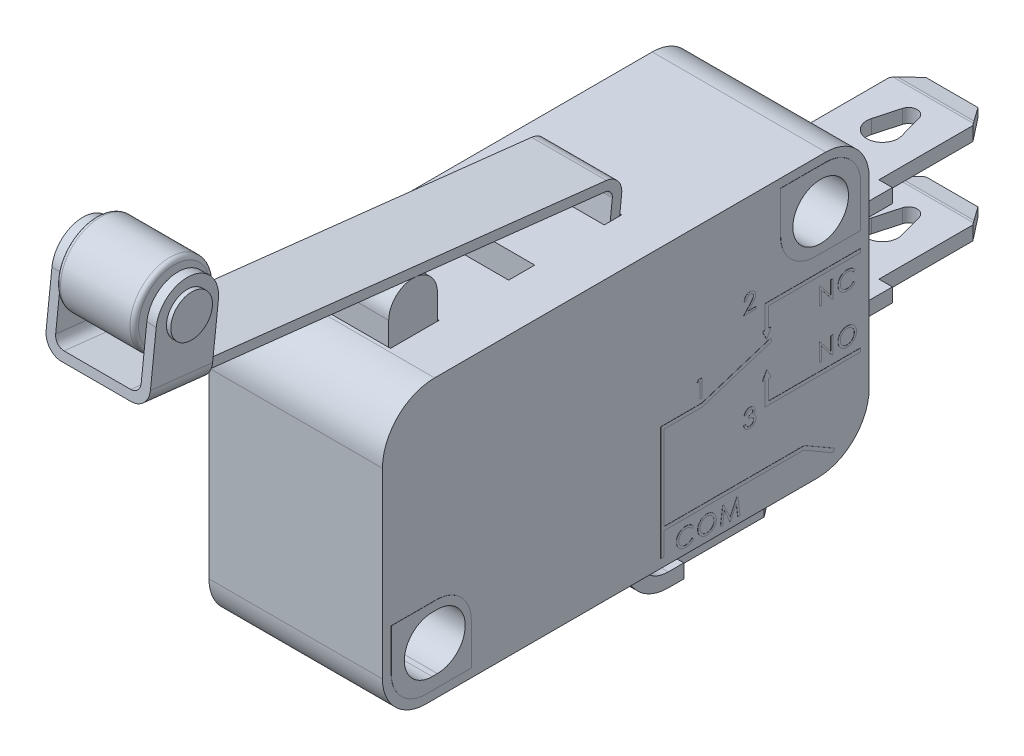
SolidWorks part; units mm, degrees
other "Switch Body"
other "Connections"
other "Lever with Wheel"
material "ABS"
ref_plane "Front Plane" through (0, 0, 0) normal (0, 0, 1) x (1, 0, 0)
ref_plane "Top Plane" through (0, 0, 0) normal (0, 1, 0) x (1, 0, 0)
ref_plane "Right Plane" through (0, 0, 0) normal (1, 0, 0) x (0, 0, -1)
sketch "Sketch1" plane through (0, 0, 0) normal (1, 0, 0) x (0, 0, -1)
  line L0 (-14, 0) -> (0, 0) construction
  line L1 (-11, 8) -> (11.5, 8)
  line L2 (-14, 5) -> (-14, -5.5)
  line L3 (-11.5, -8) -> (11, -8)
  line L4 (14, 5.5) -> (14, -5)
  line L5 (0, 0) -> (14, 0) construction
  line L6 (0, 0) -> (0, -8) construction
  line L7 (0, 0) -> (0, 8) construction
  arc A0 (-11, 8) -> (-14, 5) centre (-11, 5) ccw
  arc A1 (11, -8) -> (14, -5) centre (11, -5) ccw
  arc A2 (-14, -5.5) -> (-11.5, -8) centre (-11.5, -5.5) ccw
  arc A3 (11.5, 8) -> (14, 5.5) centre (11.5, 5.5) cw
  dimension "D3" = 3
  dimension "D4" = 2.5
  dimension "D1" = 28
  dimension "D2" = 16
extrude "Body Extrude" add sketch "Sketch1" along normal mid plane 9.98
sketch "Sketch4" plane through (4.99, 0, 0) normal (1, 0, 0) x (0, 0, -1)
  line L0 (-11.15, -5.2) -> (-10.85, -5.2) construction
  line L1 (-11.15, -3.6) -> (-10.85, -3.6)
  line L2 (-11.15, -6.8) -> (-10.85, -6.8)
  line L3 (-11.15, -5.2) -> (-12.75, -5.2) construction
  line L4 (-10.85, -5.2) -> (-9.25, -5.2) construction
  line L5 (11.2, 5.2) -> (11.2, 6.8) construction
  line L6 (11.2, 6.8) -> (11.2, 8) construction
  line L7 (11.5, 8) -> (-11, 8) construction
  line L8 (11.2, 5.2) -> (12.8, 5.2) construction
  line L9 (12.8, 5.2) -> (14, 5.2) construction
  line L10 (14, -5) -> (14, 5.5) construction
  line L11 (11.2, 5.2) -> (11.2, 3.6) construction
  line L13 (-11.5, -8) -> (11, -8) construction
  line L15 (-14, 5) -> (-14, -5.5) construction
  circle A0 centre (11.2, 5.2) radius 1.6
  arc A1 (-11.15, -3.6) -> (-11.15, -6.8) centre (-11.15, -5.2) ccw
  arc A2 (-10.85, -6.8) -> (-10.85, -3.6) centre (-10.85, -5.2) ccw
  point P4 (-11, -5.2)
  dimension "D1" = 3.2
  dimension "D2" = 3.2
  dimension "D3" = 3.5
  dimension "D4" = 1.2
  dimension "D5" = 1.2
  dimension "D6" = 2.8
  dimension "D7" = 2.8
  dimension "D8" = 11.6
  dimension "D9" = 1.2
  dimension "D10" = 3
  dimension "D11" = 2.8
  dimension "D12" = 11.6
extrude "Mount Holes Cut" cut sketch "Sketch4" against normal up to surface (9.98 mm away) up to face at (-4.99, 0, 0)
sketch "Sketch3" plane through (0, 0, 0) normal (1, 0, 0) x (0, 0, -1)
  line L0 (23.75, 2.5) -> (1.75, 2.5)
  line L1 (1.75, 2.5) -> (1.75, -11)
  line L2 (1.75, -11) -> (11.75, -11)
  line L3 (11.75, -11) -> (11.75, -10.2)
  line L4 (11.75, -10.2) -> (2.55, -10.2)
  line L5 (2.55, -10.2) -> (2.55, -3.25)
  line L6 (2.55, -3.25) -> (23.75, -3.25)
  line L7 (23.75, -3.25) -> (23.75, -2.45)
  line L8 (23.75, -2.45) -> (2.55, -2.45)
  line L9 (2.55, -2.45) -> (2.55, 1.7)
  line L10 (2.55, 1.7) -> (23.75, 1.7)
  line L11 (23.75, 1.7) -> (23.75, 2.5)
  line L12 (23.75, -2.45) -> (23.75, 1.7) construction
  line L13 (2.55, -2.45) -> (2.55, -3.25) construction
  line L14 (11.75, -11) -> (23.75, -11) construction
  line L15 (23.75, -11) -> (23.75, -3.25) construction
  line L16 (11.75, -10.2) -> (23.75, -10.2) construction
  line L17 (14, -5) -> (14, 5.5) construction
  line L18 (11.5, 8) -> (-11, 8) construction
  dimension "D1" = 0.8
  dimension "D2" = 0.8
  dimension "D3" = 10
  dimension "D4" = 12
  dimension "D5" = 5.75
  dimension "D6" = 9.75
  dimension "D7" = 19
  dimension "D8" = 5.5
extrude "Connection Extrude" add sketch "Sketch3" along normal mid plane 6.35 separate body
sketch "Sketch6" plane through (0, 0, -14) normal (0, 0, -1) x (-1, 0, 0)
  line L4 (3.175, 1.7) -> (3.175, 2.5)
  line L5 (3.175, 2.5) -> (-3.175, 2.5)
  line L6 (-3.175, 2.5) -> (-3.175, 1.7)
  line L7 (-3.175, 1.7) -> (3.175, 1.7)
  line L8 (3.175, 1.7) -> (3.175, 2.5)
  line L9 (3.175, 2.5) -> (-3.175, 2.5)
  line L10 (-3.175, 2.5) -> (-3.175, 1.7)
  line L11 (-3.175, 1.7) -> (3.175, 1.7)
  line L12 (3.175, -3.25) -> (3.175, -2.45)
  line L13 (3.175, -2.45) -> (-3.175, -2.45)
  line L14 (-3.175, -2.45) -> (-3.175, -3.25)
  line L15 (-3.175, -3.25) -> (3.175, -3.25)
  line L16 (3.175, -3.25) -> (3.175, -2.45)
  line L17 (3.175, -2.45) -> (-3.175, -2.45)
  line L18 (-3.175, -2.45) -> (-3.175, -3.25)
  line L19 (-3.175, -3.25) -> (3.175, -3.25)
  dimension "D1" = 0
  dimension "D2" = 0
extrude "Connection Cut-1" cut sketch "Sketch6" against normal blind 0.5
sketch "Sketch7" plane through (0, -8, 0) normal (0, -1, 0) x (1, 0, 0)
  line L0 (3.175, -1.75) -> (-3.175, -1.75) construction
  line L1 (-3.175, -1.75) -> (3.175, -1.75)
  line L2 (-3.175, -1.75) -> (-3.175, -2.55)
  line L3 (-3.175, -2.55) -> (3.175, -2.55)
  line L4 (3.175, -1.75) -> (3.175, -2.55)
  line L5 (3.175, -1.75) -> (3.175, -11.75) construction
  line L6 (-3.175, -1.75) -> (-3.175, -11.75) construction
  dimension "D1" = 0.8
extrude "Connection Cut-2" cut sketch "Sketch7" against normal blind 0.5
fillet "Connection Fillet-1" radius 2.5 1 edges at (0, -11, -1.75)
fillet "Connection Fillet-2" radius 1.7 1 edges at (0, -10.2, -2.55)
sketch "Sketch5" plane through (3.175, 0, 0) normal (1, 0, 0) x (0, 0, -1)
  line L0 (23.75, 2.1) -> (22.75, 2.1) construction
  line L1 (23.75, 1.7) -> (23.75, 2.5) construction
  line L2 (23.75, -2.85) -> (22.75, -2.85) construction
  line L3 (23.75, -3.25) -> (23.75, -2.45) construction
  line L4 (11.75, -10.6) -> (10.75, -10.6) construction
  line L5 (11.75, -11) -> (11.75, -10.2) construction
  line L6 (10.75, -11) -> (10.75, -10.2) construction
  line L7 (11.75, -10.2) -> (4.25, -10.2) construction
  line L8 (22.75, -2.45) -> (22.75, -3.25) construction
  line L9 (23.75, -2.45) -> (2.55, -2.45) construction
  line L10 (22.75, 2.5) -> (22.75, 1.7) construction
  line L11 (23.75, 2.5) -> (1.75, 2.5) construction
  line L12 (11.75, -10.35) -> (11.75, -10.85) construction
  line L13 (23.75, 2.35) -> (23.75, 1.85) construction
  line L14 (23.75, -2.6) -> (23.75, -3.1) construction
  line L15 (10.75, -10.2) -> (11.75, -10.2)
  line L16 (11.75, -10.2) -> (11.75, -10.35)
  line L17 (11.75, -10.35) -> (10.75, -10.2)
  line L18 (10.75, -11) -> (11.75, -11)
  line L19 (11.75, -11) -> (11.75, -10.85)
  line L20 (11.75, -10.85) -> (10.75, -11)
  line L21 (22.75, 2.5) -> (23.75, 2.5)
  line L22 (23.75, 2.5) -> (23.75, 2.35)
  line L23 (23.75, 2.35) -> (22.75, 2.5)
  line L24 (22.75, 1.7) -> (23.75, 1.7)
  line L25 (23.75, 1.7) -> (23.75, 1.85)
  line L26 (23.75, 1.85) -> (22.75, 1.7)
  line L27 (22.75, -2.45) -> (23.75, -2.45)
  line L28 (23.75, -2.45) -> (23.75, -2.6)
  line L29 (23.75, -2.6) -> (22.75, -2.45)
  line L30 (22.75, -3.25) -> (23.75, -3.25)
  line L31 (23.75, -3.25) -> (23.75, -3.1)
  line L32 (23.75, -3.1) -> (22.75, -3.25)
  dimension "D1" = 0.5
  dimension "D2" = 1
extrude "Connection Cut-3" cut sketch "Sketch5" against normal up to surface (6.35 mm away) up to face at (-3.175, -4.5193, -9.9879)
fillet "Connection Fillet-3" radius 1 6 edges at (0, 2.5, -22.75) (0, 1.7, -22.75) (0, -3.25, -22.75) (0, -2.45, -22.75) (0, -10.2, -10.75) (0, -11, -10.75)
sketch "Sketch8" plane through (0, -11, 0) normal (0, -1, 0) x (1, 0, 0)
  line L0 (0, 0) -> (0, -5.15) construction
  line L1 (0, -5.15) -> (0, -8.5) construction
  line L2 (0, -8.5) -> (0, -11.75) construction
  line L3 (-3.175, -11.75) -> (3.175, -11.75) construction
  line L4 (2.4, -5.15) -> (-2.4, -5.15) construction
  line L5 (1.5, -11.75) -> (-1.5, -11.75) construction
  line L6 (-2.4, -5.15) -> (-3.175, -5.15)
  line L7 (-3.175, -4.25) -> (-3.175, -10.6754) construction
  line L8 (-3.175, -5.15) -> (-3.175, -11.75)
  line L9 (-3.175, -10.8238) -> (-3.175, -11.75) construction
  line L10 (2.4, -5.15) -> (3.175, -5.15)
  line L11 (3.175, -4.25) -> (3.175, -10.6754) construction
  line L12 (3.175, -5.15) -> (3.175, -11.75)
  line L13 (-2.4, -5.15) -> (-2.4, -10.55)
  line L14 (-2.4, -10.55) -> (-1.5, -11.75)
  line L15 (2.4, -5.15) -> (2.4, -10.55)
  line L16 (2.4, -10.55) -> (1.5, -11.75)
  line L17 (-2.4, -10.55) -> (-3.175, -10.55) construction
  line L18 (2.4, -10.55) -> (3.175, -10.55) construction
  line L19 (-3.175, -11.75) -> (-1.5, -11.75)
  line L20 (1.5, -11.75) -> (3.175, -11.75)
  circle A0 centre (0, -8.5) radius 0.75
  dimension "D1" = 3
  dimension "D6" = 1.5
  dimension "D2" = 4.8
  dimension "D3" = 1.2
  dimension "D4" = 6.6
  dimension "D5" = 3.25
extrude "Connection Cut-4" cut sketch "Sketch8" against normal up to surface (0.8 mm away) up to face at (0, -10.2, -7.4627)
sketch "Sketch9" plane through (0, 8, 0) normal (0, 1, 0) x (1, 0, 0)
  line L0 (0, -14) -> (0, -10.8) construction
  line L1 (4.99, -14) -> (-4.99, -14) construction
  line L2 (0, -10.8) -> (0, -8) construction
  line L3 (-2.25, -8) -> (2.25, -8)
  line L4 (-2.25, -8) -> (-2.25, -10.8)
  line L5 (-2.25, -10.8) -> (2.25, -10.8)
  line L6 (2.25, -8) -> (2.25, -10.8)
  line L7 (0, -8) -> (0, -4) construction
  line L8 (0, -4) -> (0, -2.5) construction
  line L9 (-2.25, -2.5) -> (2.25, -2.5)
  line L10 (-2.25, -2.5) -> (-2.25, -4)
  line L11 (-2.25, -4) -> (2.25, -4)
  line L12 (2.25, -2.5) -> (2.25, -4)
  line L13 (0, -2.5) -> (0, 2) construction
  line L15 (-2.25, 2.5) -> (2.25, 2.5)
  line L16 (-2.25, 2.5) -> (-2.25, 1.5)
  line L17 (-2.25, 1.5) -> (2.25, 1.5)
  line L18 (2.25, 2.5) -> (2.25, 1.5)
  line L19 (-2.25, 2.5) -> (2.25, 1.5) construction
  line L20 (-2.25, 1.5) -> (2.25, 2.5) construction
  dimension "D1" = 2.8
  dimension "D2" = 4.5
  dimension "D3" = 6
  dimension "D4" = 10
  dimension "D5" = 1.5
  dimension "D6" = 16
  dimension "D7" = 1
extrude "Button Cut-1" cut sketch "Sketch9" against normal blind 4
sketch "Sketch10" plane through (0, 2.5, 0) normal (0, 1, 0) x (1, 0, 0)
  line L0 (0, 0) -> (0, 17.15) construction
  line L1 (0, 17.15) -> (0, 23.75) construction
  line L2 (-3.175, 23.75) -> (3.175, 23.75) construction
  line L3 (-2.4, 17.15) -> (2.4, 17.15) construction
  line L4 (-1.5, 23.75) -> (1.5, 23.75) construction
  line L5 (2.4, 17.15) -> (3.175, 17.15)
  line L6 (3.175, 22.6754) -> (3.175, 1.75) construction
  line L7 (3.175, 17.15) -> (3.175, 23.75)
  line L8 (3.175, 23.75) -> (1.5, 23.75)
  line L9 (1.5, 23.75) -> (2.4, 22.55)
  line L10 (2.4, 22.55) -> (2.4, 17.15)
  line L11 (-1.5, 23.75) -> (-2.4, 22.55)
  line L12 (-2.4, 22.55) -> (-2.4, 17.15)
  line L13 (-2.4, 17.15) -> (-3.175, 17.15)
  line L14 (-3.175, 22.6754) -> (-3.175, 1.75) construction
  line L15 (-3.175, 17.15) -> (-3.175, 23.75)
  line L16 (-3.175, 23.75) -> (-1.5, 23.75)
  line L17 (-0.4819, 21.3833) -> (-0.8674, 19.99)
  line L18 (0.4819, 21.3833) -> (0.8674, 19.99)
  arc A0 (-0.8674, 19.99) -> (0.8674, 19.99) centre (0, 19.75) ccw
  arc A1 (0.4819, 21.3833) -> (-0.4819, 21.3833) centre (0, 21.25) ccw
  dimension "D5" = 1
  dimension "D6" = 1.8
  dimension "D1" = 3
  dimension "D2" = 4.8
  dimension "D3" = 6.6
  dimension "D4" = 1.2
  dimension "D7" = 1.5
  dimension "D8" = 4
extrude "Connection Cut-5" cut sketch "Sketch10" against normal up to surface (5.75 mm away) up to face at (0, -3.25, -12.6127)
sketch "Sketch21" plane through (4.99, 0, 0) normal (1, 0, 0) x (0, 0, -1)
  line L0 (11.5, 8) -> (-11, 8) construction
  line L1 (8.9, 7.5) -> (11.5, 7.5)
  line L2 (8.9, 7.5) -> (8.9, 5.1)
  line L3 (10.9, 3.1) -> (13.5, 3.1)
  line L4 (13.5, 5.5) -> (13.5, 3.1)
  line L5 (-10.9, -3.1) -> (-13.5, -3.1)
  line L6 (-8.9, -5.1) -> (-8.9, -7.5)
  line L7 (-8.9, -7.5) -> (-11.5, -7.5)
  line L8 (-13.5, -3.1) -> (-13.5, -5.5)
  line L9 (14, -5) -> (14, 5.5) construction
  line L10 (-11.5, -8) -> (11, -8) construction
  line L11 (-14, 5) -> (-14, -5.5) construction
  line L12 (-11.15, -6.8) -> (-10.85, -6.8) construction
  line L13 (-10.85, -3.6) -> (-11.15, -3.6) construction
  line L14 (-11.15, -6.8) -> (-10.85, -6.8)
  line L15 (-10.85, -3.6) -> (-11.15, -3.6)
  arc A0 (-10.9, -3.1) -> (-8.9, -5.1) centre (-10.9, -5.1) cw
  arc A1 (8.9, 5.1) -> (10.9, 3.1) centre (10.9, 5.1) ccw
  arc A2 (11.5, 7.5) -> (13.5, 5.5) centre (11.5, 5.5) cw
  arc A3 (-11.5, -7.5) -> (-13.5, -5.5) centre (-11.5, -5.5) cw
  arc A4 (-10.85, -6.8) -> (-10.85, -3.6) centre (-10.85, -5.2) ccw construction
  arc A5 (-11.15, -3.6) -> (-11.15, -6.8) centre (-11.15, -5.2) ccw construction
  arc A6 (-10.85, -6.8) -> (-10.85, -3.6) centre (-10.85, -5.2) ccw
  arc A7 (-11.15, -3.6) -> (-11.15, -6.8) centre (-11.15, -5.2) ccw
  circle A8 centre (11.2, 5.2) radius 1.6 construction
  circle A9 centre (11.2, 5.2) radius 1.6
  dimension "D9" = 2
  dimension "D1" = 4.6
  dimension "D2" = 4.6
  dimension "D3" = 4.4
  dimension "D4" = 4.4
  dimension "D5" = 0.5
  dimension "D6" = 0.5
  dimension "D7" = 0.5
  dimension "D8" = 0.5
extrude "Mount Extension" add sketch "Sketch21" along normal blind 0.01
mirror "Mirror Mount Extension" about plane through (0, 0, 0) normal (1, 0, 0) of "Mount Extension"
sketch "Sketch22" plane through (4.99, 0, 0) normal (1, 0, 0) x (0, 0, -1)
  line L0 (23.75, 2.1) -> (14, 2.1) construction
  line L1 (23.75, 1.85) -> (23.75, 2.35) construction
  line L2 (14, -5) -> (14, 5.5) construction
  line L3 (14, 2.1) -> (13.5, 2.1) construction
  line L4 (23.75, -2.85) -> (14, -2.85) construction
  line L5 (23.75, -3.1) -> (23.75, -2.6) construction
  line L6 (14, -2.85) -> (13.5, -2.85) construction
  line L7 (13.5, 2.2) -> (13.5, 2)
  line L8 (13.5, -2.75) -> (13.5, -2.95)
  line L9 (13.5, 2.2) -> (8, 2.2)
  line L10 (13.5, -2.95) -> (8, -2.95)
  line L11 (8, 2.2) -> (8, 0.875)
  line L12 (8, -2.95) -> (8, -1.625)
  line L13 (13.5, 2) -> (8.2, 2)
  line L14 (8.2, 2) -> (8.2, 0.875)
  line L15 (8, 0.875) -> (8.2, 0.875) construction
  line L16 (13.5, -2.75) -> (8.2, -2.75)
  line L17 (8.2, -2.75) -> (8.2, -1.625)
  line L18 (8.2, -1.625) -> (8, -1.625) construction
  line L19 (8.2, 0.875) -> (8.35, 0.875)
  line L20 (8, 0.875) -> (7.85, 0.875)
  line L21 (8.1, 0.875) -> (8.1, 0.375) construction
  line L22 (7.85, 0.875) -> (8.1, 0.375)
  line L23 (8.1, 0.375) -> (8.35, 0.875)
  line L24 (8.2, -1.625) -> (8.35, -1.625)
  line L25 (8, -1.625) -> (7.85, -1.625)
  line L26 (8.1, -1.625) -> (8.1, -1.125) construction
  line L27 (7.85, -1.625) -> (8.1, -1.125)
  line L28 (8.1, -1.125) -> (8.35, -1.625)
  line L29 (-11.5, -8) -> (11, -8) construction
  line L30 (4.5, -1) -> (8.35, 0.225) construction
  line L31 (8.35, 0.225) -> (8.35, 0.875) construction
  line L32 (8.3197, 0.3203) -> (8.3803, 0.1297)
  line L33 (8.3197, 0.3203) -> (4.3631, -0.9386)
  line L34 (4.3631, -0.9386) -> (2, -0.9386)
  line L35 (2, -0.9386) -> (2, -7.5)
  line L36 (2, -7.5) -> (2.2, -7.5)
  line L37 (2.2, -7.5) -> (2.2, -6.2)
  line L38 (2.2, -1.1386) -> (4.3942, -1.1386)
  line L39 (4.3942, -1.1386) -> (8.3803, 0.1297)
  line L40 (2.2, -6) -> (10.2679, -6)
  line L41 (10.2679, -6) -> (12, -7)
  line L42 (12, -7) -> (11.9, -7.1732)
  line L43 (11.9, -7.1732) -> (10.2144, -6.2)
  line L44 (10.2144, -6.2) -> (2.2, -6.2)
  line L45 (2.2, -6) -> (2.2, -1.1386)
  line L46 (2.2, -6) -> (2.2, -6.2) construction
  circle A0 centre (4.5, -1) radius 0.15 construction
  dimension "D7" = 7
  dimension "D8" = 0.3
  dimension "D9" = 9.5
  dimension "D1" = 0.5
  dimension "D2" = 0.2
  dimension "D3" = 5.5
  dimension "D4" = 0.5
  dimension "D5" = 0.5
  dimension "D6" = 1.5
  dimension "D10" = 0.2
  dimension "D11" = 0.65
  dimension "D12" = 0.2
  dimension "D13" = 0.5
  dimension "D14" = 0.2
  dimension "D15" = 12
  dimension "D16" = 2
  dimension "D17" = 0.2
  dimension "D18" = 0.2
  dimension "D19" = 2
  dimension "D20" = 150
  dimension "D21" = 10
extrude "Schematic Lines" add sketch "Sketch22" along normal blind 0.01
sketch "Sketch23" plane through (4.99, 0, 0) normal (1, 0, 0) x (0, 0, -1)
  line L0 (8, 2.2) -> (6.25, 2.2) construction
  line L1 (5.1731, -0.6809) -> (3.4231, -0.6809) construction
  line L2 (8, -3.55) -> (6.25, -3.55) construction
  line L3 (2.55, -7.6327) -> (6.8929, -7.6327) construction
  line L4 (2.55, -8.5) -> (2.55, -3.25) construction
  line L5 (13.5, 0.5) -> (11, 0.5) construction
  line L6 (13.5, 0.5) -> (13.5, -2.3) construction
  line L7 (13.5, -2.3) -> (11, -2.3) construction
  line L8 (8, 2.2) -> (8, 0.875) construction
  line L9 (8, 2.2) -> (8, 0.875) construction
  line L10 (14, -5) -> (14, 5.5) construction
  line L11 (8.2, 2) -> (13.5, 2) construction
  line L12 (8.3197, 0.3203) -> (4.3631, -0.9386) construction
  line L13 (8, -3.55) -> (8, -2.95) construction
  text T0 "1" font "Century Gothic" height 1
  text T1 "2" font "Century Gothic" height 1
  text T2 "3" font "Century Gothic" height 1
  text T3 "COM" font "Century Gothic" height 1
  text T4 "NC" font "Century Gothic" height 1
  text T5 "NO" font "Century Gothic" height 1
  dimension "D1" = 0.5
  dimension "D2" = 1.5
  dimension "D3" = 2.8
  dimension "D4" = 2.5
  dimension "D5" = 1.75
  dimension "D6" = 0.85
  dimension "D7" = 0.6
extrude "Schematic Text" add sketch "Sketch23" along normal blind 0.01
sketch "Sketch24" plane through (-4.99, 0, 0) normal (-1, 0, 0) x (0, 0, 1)
  line L0 (-14, 2) -> (-4, 2) construction
  line L1 (-14, -5) -> (-14, 5.5) construction
  line L2 (-4, 2) -> (14, 2) construction
  line L3 (14, 5) -> (14, -5.5) construction
  line L4 (-11.5, 8) -> (11, 8) construction
  text T0 "16(5)A  250V~μ\r\n1E4  T125\r\n16A  125V~" font "Century Gothic" height 1.3
  dimension "D1" = 10
  dimension "D2" = 6
extrude "Specs Text" add sketch "Sketch24" along normal blind 0.01
sketch "Sketch11" plane through (0, 0, 0) normal (1, 0, 0) x (0, 0, -1)
  line L0 (2, 8) -> (2, 0) construction
  line L1 (2.5, 8) -> (1.5, 8) construction
  line L2 (2, 0) -> (0, 0) construction
  circle A0 centre (2, 6) radius 0.75
  dimension "D1" = 2
  dimension "D2" = 1.5
extrude "Button Cut-2" cut sketch "Sketch11" against normal mid plane 4.3
sketch "Sketch Set 0.25 or 2.75" plane through (0, 0, 0) normal (1, 0, 0) x (0, 0, -1)
  line L0 (-8, 4) -> (-10.8, 4) construction
  line L2 (-10.8, 6.75) -> (-8, 6.75)
  line L4 (-9.4, 4) -> (-9.4, 6.75) construction
  line L5 (-10.8, 6.75) -> (-10.8, 9.35)
  line L6 (-10.8, 9.35) -> (-8, 9.35) construction
  line L7 (-8, 9.35) -> (-8, 6.75)
  line L8 (-9.4, 6.75) -> (-9.4, 9.35) construction
  line L9 (-9.4, 9.35) -> (-9.4, 10.75) construction
  line L10 (11.5, 8) -> (-11, 8) construction
  arc A0 (-8, 9.35) -> (-10.8, 9.35) centre (-9.4, 9.35) ccw
  dimension "D2" = 4
  dimension "D1" = 2.8
  dimension "D3" = 2.75
extrude "Switch Button ADJUSTABLE" add sketch "Sketch Set 0.25 or 2.75" along normal mid plane 4.3 separate body
sketch "Sketch13" plane through (0, 0, 0) normal (1, 0, 0) x (0, 0, -1)
  line L0 (1.7317, 6.0301) -> (2.2683, 5.9699) construction
  line L1 (1.8096, 6.7254) -> (2.0657, 9.0114)
  line L2 (1.6597, 9.5198) -> (-25.4705, 12.5591)
  line L3 (2.3462, 6.6653) -> (2.6023, 8.9513)
  line L4 (1.7199, 10.0564) -> (-21.8328, 12.695)
  line L5 (-25.4104, 13.0957) -> (-25.0252, 16.5342) construction
  line L6 (-21.8328, 12.695) -> (-21.4476, 16.1334) construction
  line L7 (-25.0252, 16.5342) -> (-21.4476, 16.1334) construction
  line L8 (2, 6) -> (2.334, 8.9814) construction
  line L9 (1.7317, 6.0301) -> (1.8096, 6.7254) construction
  line L10 (2.2683, 5.9699) -> (2.3462, 6.6653) construction
  line L11 (-21.8328, 12.695) -> (-25.4104, 13.0957)
  line L12 (-25.4104, 13.0957) -> (-25.4705, 12.5591)
  line L13 (-23.2364, 16.3338) -> (-23.4925, 14.0481) construction
  line L14 (-23.2364, 16.3338) -> (-23.6216, 12.8953) construction
  line L15 (2.0657, 9.0114) -> (2.6023, 8.9513) construction
  line L16 (-23.2364, 16.3338) -> (-22.9803, 18.6195) construction
  arc A0 (1.8096, 6.7254) -> (2.3462, 6.6653) centre (2, 6) ccw
  arc A2 (-21.4476, 16.1334) -> (-25.0252, 16.5342) centre (-23.2364, 16.3338) ccw construction
  arc A3 (2.6023, 8.9513) -> (1.7199, 10.0564) centre (1.6085, 9.0626) ccw
  arc A4 (2.0657, 9.0114) -> (1.6597, 9.5198) centre (1.6085, 9.0626) ccw
  circle A5 centre (-23.2364, 16.3338) radius 2.3 construction
  arc A6 (-8, 9.35) -> (-10.8, 9.35) centre (-9.4, 9.35) ccw construction
  dimension "D1" = 1.5
  dimension "D5" = 4
  dimension "D6" = 1
  dimension "D7" = 0.46
  dimension "D8" = 28.3
  dimension "D10" = 4.6
  dimension "D2" = 0.54
  dimension "D3" = 0.54
  dimension "D4" = 3.6
  dimension "D9" = 4
  dimension "D11" = 6.3
extrude "Switch Lever Extrude" add sketch "Sketch13" along normal mid plane 4.3 separate body
sketch "Sketch15" plane through (0, 10.122, -1.1339) normal (0, 0.9938, -0.1113) x (1, 0, 0)
  line L0 (0, -26.7104) -> (0, -22.8604) construction
  line L1 (2.15, -26.7104) -> (-2.15, -26.7104) construction
  line L2 (-1.65, -22.8604) -> (1.65, -22.8604) construction
  line L4 (1.65, -22.8604) -> (2.15, -22.8604) construction
  line L5 (2.15, 0.5896) -> (2.15, -26.7104) construction
  line L6 (-1.65, -22.8604) -> (-2.15, -22.8604) construction
  line L7 (-2.15, 0.5896) -> (-2.15, -26.7104) construction
  line L8 (-1.9, -22.6104) -> (-1.9, -23.1104) construction
  line L9 (1.9, -22.6104) -> (1.9, -23.1104) construction
  line L10 (2.15, -22.6104) -> (2.15, -23.1104)
  line L11 (-2.15, -22.6104) -> (-2.15, -23.1104)
  line L12 (1.9, -22.6104) -> (2.15, -22.6104)
  line L13 (1.9, -23.1104) -> (2.15, -23.1104)
  line L14 (-1.9, -22.6104) -> (-2.15, -22.6104)
  line L15 (-1.9, -23.1104) -> (-2.15, -23.1104)
  arc A0 (1.9, -22.6104) -> (1.9, -23.1104) centre (1.9, -22.8604) ccw
  arc A1 (-1.9, -23.1104) -> (-1.9, -22.6104) centre (-1.9, -22.8604) ccw
  dimension "D1" = 3.6
  dimension "D2" = 0.5
extrude "Lever Cut-1" cut sketch "Sketch15" against normal up to surface (0.54 mm away) up to face at (0, 11.0394, 11.9054)
sketch "Sketch16" plane through (0, 2.9737, 26.5444) normal (0, 0.1113, 0.9938) x (1, 0, 0)
  line L0 (2.15, 9.6454) -> (3, 9.6454)
  line L1 (3, 9.6454) -> (3, 15.4454)
  line L2 (-2.15, 9.6454) -> (-3, 9.6454)
  line L3 (-3, 9.6454) -> (-3, 15.4454)
  line L4 (-3, 15.4454) -> (-2.46, 15.4454)
  line L5 (-2.46, 15.4454) -> (-2.46, 10.1854)
  line L6 (3, 15.4454) -> (2.46, 15.4454)
  line L7 (2.46, 15.4454) -> (2.46, 10.1854)
  line L8 (2.46, 10.1854) -> (2.15, 10.1854)
  line L9 (-2.46, 10.1854) -> (-2.15, 10.1854)
  line L10 (-2.15, 10.1854) -> (-2.15, 9.6454)
  line L11 (2.15, 10.1854) -> (2.15, 9.6454)
  dimension "D1" = 6
  dimension "D2" = 5.8
extrude "Lever Side Tabs" add sketch "Sketch16" against normal up to surface (3.6 mm away) up to face at (2.025, 12.4266, 21.8629)
fillet "Lever Fillet-1" 2 edges at (2.73, 18.323, 24.8248) (2.73, 17.9223, 21.2472) type full round first side face at (0, 15.5752, 25.1327) second side face at (2.4533, 14.2585, 21.6576) middle face at (2.73, 18.1226, 23.036)
fillet "Lever Fillet-2" 2 edges at (-2.73, 18.323, 24.8248) (-2.73, 17.9223, 21.2472) type full round first side face at (0, 15.128, 25.1828) second side face at (-2.4533, 14.2585, 21.6576) middle face at (-2.73, 18.1226, 23.036)
fillet "Lever Fillet-3" radius 0.54 2 edges at (2.46, 12.8953, 23.6216) (-2.46, 12.8953, 23.6216)
fillet "Lever Fillet-4" radius 1 2 edges at (-3, 12.3587, 23.6817) (3, 12.3587, 23.6817)
sketch "Sketch18" plane through (0, 0, 0) normal (1, 0, 0) x (0, 0, -1)
  line L0 (-25.0252, 16.5342) -> (-21.4476, 16.1334) construction
  circle A0 centre (-23.2364, 16.3338) radius 1.2
  dimension "D1" = 2.4
extrude "Lever Shaft" add sketch "Sketch18" along normal mid plane 6.5
sketch "Sketch19" plane through (0, 0, 0) normal (1, 0, 0) x (0, 0, -1)
  circle A0 centre (-23.2364, 16.3338) radius 2.3 construction
  circle A1 centre (-23.2364, 16.3338) radius 2.3
extrude "Lever Wheel" add sketch "Sketch19" along normal mid plane 4.5
fillet "Lever Wheel Fillet-1" radius 0.25 2 edges at (-2.25, 16.3338, 20.9364) (2.25, 16.3338, 20.9364)
sketch "Sketch25" plane through (0, 0, 0) normal (1, 0, 0) x (0, 0, -1)
  line L0 (-11.5, -8) -> (11, -8) construction
  line L1 (-14, 5) -> (-14, -5.5) construction
  circle A0 centre (-2, 0) radius 3
  dimension "D1" = 6
  dimension "D2" = 8
  dimension "D3" = 12
extrude "Hollow Cut" cut sketch "Sketch25" against normal mid plane 2
sketch "Sketch26" plane through (0, 0, 0) normal (1, 0, 0) x (0, 0, -1)
  circle A0 centre (-2, 0) radius 2.05
  dimension "D1" = 4.1
extrude "Real-World Weight Adjustment" add sketch "Sketch26" along normal mid plane 2 separate body
